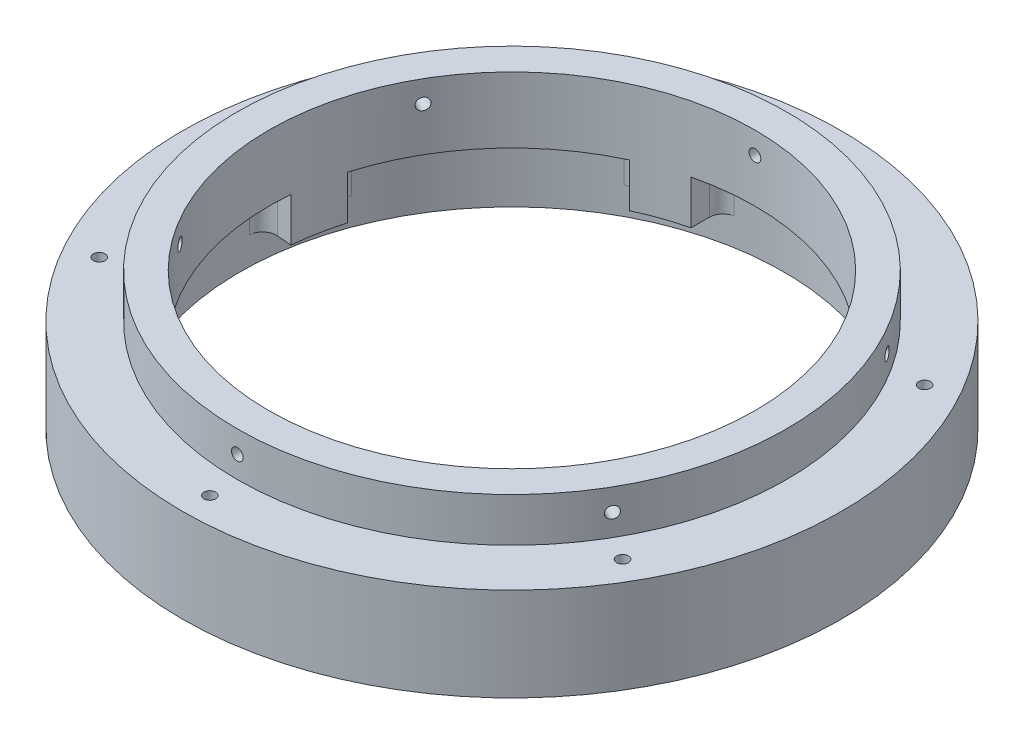
SolidWorks part; units mm, degrees
ref_plane "Front Plane" through (0, 0, 0) normal (0, 0, 1) x (1, 0, 0)
ref_plane "Top Plane" through (0, 0, 0) normal (0, 1, 0) x (1, 0, 0)
ref_plane "Right Plane" through (0, 0, 0) normal (1, 0, 0) x (0, 0, -1)
sketch "Sketch1" plane through (0, 0, 0) normal (0, 1, 0) x (1, 0, 0)
  circle A0 centre (0, 0) radius 63.5
  circle A1 centre (0, 0) radius 76.2
  circle A2 centre (0, 0) radius 56.1975
  circle A4 centre (0, 0) radius 62.865
  dimension "D1" = 152.4
  dimension "D3" = 112.395
  dimension "D2" = 12.7
  dimension "D4" = 13.335
extrude "Boss-Extrude1" add sketch "Sketch1" along normal blind 15.24 contours A0 A2 | A0 A4 region at (-63.3204, 0, 0) region at (-61.0869, 0, 0)
extrude "Boss-Extrude2" add sketch "Sketch1<4>" along normal blind 5.08 and the other way blind 16.51 contours A1 A0 | A0 A4 region at (-63.3204, 0, 0) region at (-74.0447, 0, 0)
sketch "Sketch1<4>" plane through (0, 0, 0) normal (0, 1, 0) x (1, 0, 0) same geometry as "Sketch1"
sketch "Sketch3" plane through (0, -16.51, 0) normal (0, -1, 0) x (1, 0, 0)
  line L0 (0, 0) -> (-68.319, 5.9771) construction
  line L1 (0, 0) -> (0, 69.85) construction
  line L2 (0, 0) -> (48.9804, 58.3726)
  line L3 (0, 0) -> (13.232, 75.0424)
  line L4 (-13.2113, -54.6225) -> (-13.2113, -60.147)
  line L5 (13.2113, -54.6225) -> (13.2113, -60.147)
  line L6 (-13.2113, -60.147) -> (13.2113, -60.147)
  line L7 (-13.2113, -60.147) -> (-13.2113, -61.4611)
  line L8 (-23.7501, -50.9322) -> (-26.5679, -56.975)
  line L9 (0, 0) -> (-23.7501, -50.9322) construction
  circle A0 centre (-68.319, 5.9771) radius 4.8895
  circle A1 centre (0, 69.85) radius 1.3589
  circle A2 centre (0, 0) radius 76.2 construction
  circle A5 centre (0, 0) radius 56.1975 construction
  arc A7 (-26.5679, -56.975) -> (-13.2113, -61.4611) centre (0, 0) ccw
  arc A9 (-23.7501, -50.9322) -> (-13.2113, -54.6225) centre (0, 0) ccw
  circle A12 centre (0, 0) radius 62.865 construction
  point P0 (0, -60.147)
  dimension "D4" = 9.779
  dimension "D5" = 2.7178
  dimension "D2" = 85
  dimension "D3" = 69.85
  dimension "D6" = 30
  dimension "D7" = 10
  dimension "D9" = 26.4227
  dimension "D8" = 5.5245
  dimension "D10" = 25
extrude "Cut-Extrude1" cut sketch "Sketch3" against normal blind 15.24 contours A0 region at (-68.319, -16.51, 5.9771)
extrude "Cut-Extrude2" cut sketch "Sketch3<3>" against normal through all contours A1 region at (0, -16.51, 69.85)
sketch "Sketch3<3>" plane through (0, -16.51, 0) normal (0, -1, 0) x (1, 0, 0) same geometry as "Sketch3"
pattern_circular "CirPattern1" count 3 over 360 about axis through (0, -16.51, 0) along (0, 1, 0) of "Cut-Extrude1"
pattern_circular "CirPattern2" count 6 over 360 about axis through (0, -16.51, 0) along (0, 1, 0) of "Cut-Extrude2"
ref_plane "Plane1" through (0, 0, 76.2) normal (0, 0, 1) x (1, 0, 0)
sketch "Sketch5" plane through (0, 0, 76.2) normal (0, 0, 1) x (1, 0, 0)
  line L0 (0, -16.51) -> (0, 10.16) construction
  line L1 (-1.3589, -16.51) -> (1.3589, -16.51) construction
  circle A0 centre (0, 10.16) radius 1.3589
  dimension "D2" = 2.7178
  dimension "D1" = 26.67
extrude "Cut-Extrude3" cut sketch "Sketch5" against normal up to surface (132.3811 mm away) up to face at (0, 15.24, 56.1975)
extrude "Boss-Extrude3" add sketch "Sketch3<11>" along normal blind 10.16 from surface contours L4 A9 L8 A7 L7 starting at face at (0, 0, 56.1975)
sketch "Sketch3<11>" plane through (0, -16.51, 0) normal (0, -1, 0) x (1, 0, 0) same geometry as "Sketch3"
pattern_circular "CirPattern3" count 6 over 360 about axis through (0, 15.24, 0) along (0, 1, 0) of "Cut-Extrude3", "Boss-Extrude3"
fillet "Fillet1" radius 3.175 12 edges at (-62.6258, -5.08, -5.479) (-59.8326, -5.08, -19.2892) (-26.5679, -5.08, -56.975) (-13.2113, -5.08, -61.4611) (36.0579, -5.08, -51.496) (46.6212, -5.08, -42.1719) (62.6258, -5.08, 5.479) (59.8326, -5.08, 19.2892) (26.5679, -5.08, 56.975) (13.2113, -5.08, 61.4611) (-36.0579, -5.08, 51.496) (-46.6212, -5.08, 42.1719)
equation "\"Middle Coupler Inner Daimeter\"= 3.875in"
equation "\"Middle Coupler  Wall Thickness\" = 0.25in"
equation "\"Middle Coupler Bottom Thickness\"= 0.2in"
equation "\"Bearing Rail Offset\"= 0.45in"
equation "\"3-56 UNF Tap\"= 0.089in"
equation "\"3-48 Tap\"= 0.079in"
equation "\"3-56 UNF Clearance\"= 0.104in"
equation "\"3-48 Clearance\" = 0.104in"
equation "\"Ball Bearing Distance\"= 0.03in"
equation "\"TCA Outer Diameter\" = 6in"
equation "\"Interstage Aeroframe Wall Thickness\" = 0.072in"
equation "\"Compression Spring OD\"= 0.42in"
equation "\"10-24 Tap\"= 0.157in"
equation "\"10-24 Clearance\"= 0.196in"
equation "\"Lower Stage Fuselage Wall Thickness\" = 0.25in"
equation "\"6-32 Tap\" = 0.107in"
equation "\"6-32 Clearance\" = 0.144"
equation "\"1/4-20 Tap\" = 0.201in"
equation "\"12-24 Tap\" = 0.177in"
equation "\"D1@Sketch1\"=\"TCA Outer Diameter\""
equation "\"D5@Sketch3\"=\"6-32 Tap\""
equation "\"D1@Sketch5\"=\"D2@Boss-Extrude2\"+(\"D1@Boss-Extrude2\"+\"D1@Boss-Extrude1\")/2"
equation "\"D2@Sketch5\"=\"6-32 Tap\""
equation "\"D8@Sketch3\"=3/16+0.03"
equation "\"D3@Sketch1\"=\"Middle Coupler Inner Daimeter\" + 0.55"
equation "\"D4@Sketch3\"=0.375 + 0.01"
